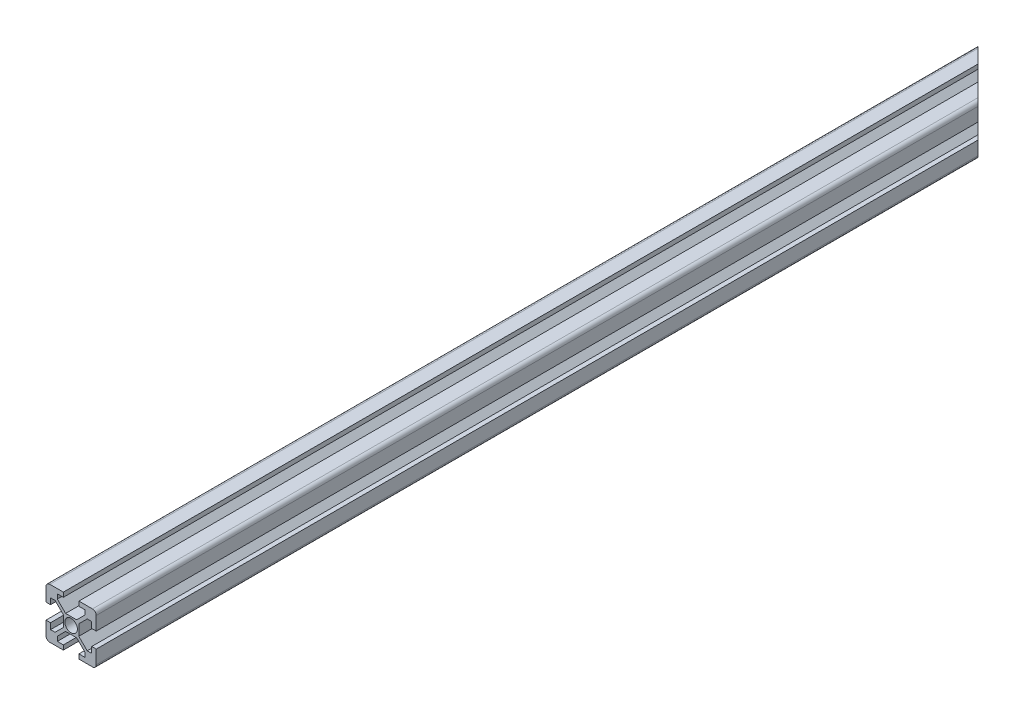
SolidWorks part; units mm, degrees
ref_plane "前视基准面" through (0, 0, 0) normal (0, 0, 1) x (1, 0, 0)
ref_plane "上视基准面" through (0, 0, 0) normal (0, 1, 0) x (1, 0, 0)
ref_plane "右视基准面" through (0, 0, 0) normal (1, 0, 0) x (0, 0, -1)
sketch "草图1" plane through (0, 0, 0) normal (0, 0, 1) x (1, 0, 0)
  line L0 (-10, -3.1) -> (-8.2, -3.1)
  line L1 (-8.5, 10) -> (8.5, 10)
  line L2 (-10, 8.5) -> (-10, -8.5)
  line L3 (-8.5, -10) -> (8.5, -10)
  line L4 (10, 8.5) -> (10, -8.5)
  line L5 (-10, 10) -> (10, -10) construction
  line L6 (-10, -10) -> (10, 10) construction
  line L7 (-3.0541, 3.1) -> (3.0541, 3.1)
  line L8 (-3.0541, 3.1) -> (-3.0541, -3.1)
  line L9 (-3.0541, -3.1) -> (3.0541, -3.1)
  line L10 (3.0541, 3.1) -> (3.0541, -3.1)
  line L11 (-3.0541, 3.1) -> (3.0541, -3.1) construction
  line L12 (-3.0541, -3.1) -> (3.0541, 3.1) construction
  line L13 (-8.2, -3.1) -> (-8.2, -5.5)
  line L14 (-8.2, -5.5) -> (-6.3971, -5.5)
  line L15 (-6.3971, -5.5) -> (-3.0541, -2.1571)
  line L16 (-5.5, 6.3971) -> (-2.1571, 3.0541)
  line L17 (-5.5, 8.2) -> (-5.5, 6.3971)
  line L18 (-3.1, 8.2) -> (-5.5, 8.2)
  line L19 (-3.1, 10) -> (-3.1, 8.2)
  line L20 (6.3971, 5.5) -> (3.0541, 2.1571)
  line L21 (8.2, 5.5) -> (6.3971, 5.5)
  line L22 (8.2, 3.1) -> (8.2, 5.5)
  line L23 (10, 3.1) -> (8.2, 3.1)
  line L24 (5.5, -6.3971) -> (2.1571, -3.0541)
  line L25 (5.5, -8.2) -> (5.5, -6.3971)
  line L26 (3.1, -8.2) -> (5.5, -8.2)
  line L27 (3.1, -10) -> (3.1, -8.2)
  line L28 (-3.1, -10) -> (-3.1, -8.2)
  line L29 (-3.1, -8.2) -> (-5.5, -8.2)
  line L30 (-5.5, -8.2) -> (-5.5, -6.3971)
  line L31 (-5.5, -6.3971) -> (-2.1571, -3.0541)
  line L32 (-8.2, 5.5) -> (-6.3971, 5.5)
  line L33 (-6.3971, 5.5) -> (-3.0541, 2.1571)
  line L34 (-8.2, 3.1) -> (-8.2, 5.5)
  line L35 (-10, 3.1) -> (-8.2, 3.1)
  line L36 (5.5, 8.2) -> (5.5, 6.3971)
  line L37 (5.5, 6.3971) -> (2.1571, 3.0541)
  line L38 (3.1, 8.2) -> (5.5, 8.2)
  line L39 (3.1, 10) -> (3.1, 8.2)
  line L40 (8.2, -5.5) -> (6.3971, -5.5)
  line L41 (6.3971, -5.5) -> (3.0541, -2.1571)
  line L42 (8.2, -3.1) -> (8.2, -5.5)
  line L43 (10, -3.1) -> (8.2, -3.1)
  circle A0 centre (0, 0) radius 2.5
  arc A1 (-10, 8.5) -> (-8.5, 10) centre (-8.5, 8.5) cw
  arc A2 (-10, -8.5) -> (-8.5, -10) centre (-8.5, -8.5) ccw
  arc A3 (8.5, 10) -> (10, 8.5) centre (8.5, 8.5) cw
  arc A4 (10, -8.5) -> (8.5, -10) centre (8.5, -8.5) cw
  point P0 (0, 0)
  point P20 (0, 0)
  point P26 (0, 0)
  point P32 (0, 0)
  point P38 (0, 0)
  point P60 (0, 0)
  dimension "D1" = 4
  dimension "D3" = 1.5
  dimension "D4" = 1.5
  dimension "D5" = 1.5
  dimension "D2" = 4
extrude "凸台-拉伸1" add sketch "草图1" along normal blind 371 contours A1 L2 L35 L34 L32 L33 L8 L7 L16 L17 L18 L19 L1 | A3 L1 L39 L38 L36 L37 L7 L10 L20 L21 L22 L23 L4 | L10 L7 L8 L9 A0 | A4 L4 L43 L42 L40 L41 L10 L9 L24 L25 L26 L27 L3 | L2 A2 L3 L28 L29 L30 L31 L9 L8 L15 L14 L13 L0 region at (-6.9209, -6.9203, 0) region at (-6.9209, 6.9203, 0) region at (-2.9671, 0, 0) region at (6.9209, -6.9203, 0) region at (6.9209, 6.9203, 0)
sketch "草图2" plane through (0, 10, 0) normal (0, 1, 0) x (1, 0, 0)
  line L0 (10, 0) -> (10, -20)
  line L1 (10, -371) -> (10, 0) construction
  line L2 (10, -20) -> (-10, 0)
  line L3 (-10, 0) -> (10, 0)
extrude "切除-拉伸1" cut sketch "草图2" against normal through all
